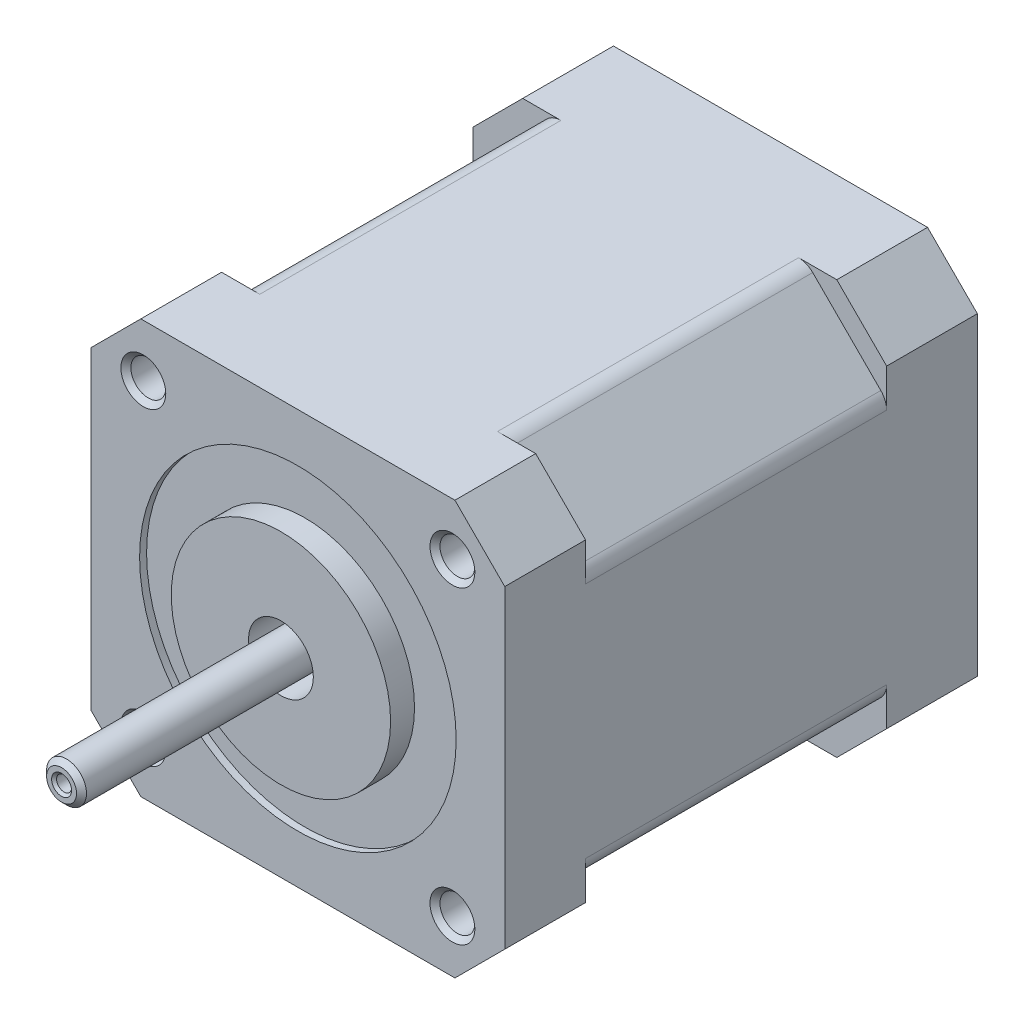
SolidWorks part; units mm, degrees
ref_plane "Front Plane" through (0, 0, 0) normal (0, 0, 1) x (1, 0, 0)
ref_plane "Top Plane" through (0, 0, 0) normal (0, 1, 0) x (1, 0, 0)
ref_plane "Right Plane" through (0, 0, 0) normal (1, 0, 0) x (0, 0, -1)
sketch "Sketch1" plane through (0, 0, 0) normal (0, 0, 1) x (1, 0, 0)
  line L0 (15.75, 20.75) -> (20.75, 15.75)
  line L1 (-15.75, 20.75) -> (15.75, 20.75)
  line L2 (-20.75, 15.75) -> (-20.75, -15.75)
  line L3 (-15.75, -20.75) -> (15.75, -20.75)
  line L4 (20.75, 15.75) -> (20.75, -15.75)
  line L5 (-20.75, 20.75) -> (20.75, -20.75) construction
  line L6 (-20.75, -20.75) -> (20.75, 20.75) construction
  line L7 (-20.75, 15.75) -> (-15.75, 20.75)
  line L8 (-20.75, -15.75) -> (-15.75, -20.75)
  line L9 (15.75, -20.75) -> (20.75, -15.75)
  point P0 (0, 0)
  dimension "D1" = 41.5
  dimension "D2" = 41.5
extrude "Boss-Extrude1" add sketch "Sketch1" along normal blind 9.1
sketch "Sketch2" plane through (0, 0, 9.1) normal (0, 0, 1) x (1, 0, 0)
  line L0 (13.3358, 20.1642) -> (20.1642, 13.3358)
  line L1 (-11.9216, -20.75) -> (11.9216, -20.75)
  line L2 (-20.75, -11.9216) -> (-20.75, 11.9216)
  line L3 (-11.9216, 20.75) -> (11.9216, 20.75)
  line L4 (20.75, -11.9216) -> (20.75, 11.9216)
  line L5 (-20.75, -20.75) -> (20.75, 20.75) construction
  line L6 (-20.75, 20.75) -> (20.75, -20.75) construction
  line L7 (-20.1642, 13.3358) -> (-13.3358, 20.1642)
  line L8 (-20.1642, -13.3358) -> (-13.3358, -20.1642)
  line L9 (13.3358, -20.1642) -> (20.1642, -13.3358)
  arc A0 (-13.3358, -20.1642) -> (-11.9216, -20.75) centre (-11.9216, -18.75) ccw
  arc A1 (-20.1642, -13.3358) -> (-20.75, -11.9216) centre (-18.75, -11.9216) cw
  arc A2 (-20.1642, 13.3358) -> (-20.75, 11.9216) centre (-18.75, 11.9216) ccw
  arc A3 (-13.3358, 20.1642) -> (-11.9216, 20.75) centre (-11.9216, 18.75) cw
  arc A4 (13.3358, 20.1642) -> (11.9216, 20.75) centre (11.9216, 18.75) ccw
  arc A5 (20.1642, 13.3358) -> (20.75, 11.9216) centre (18.75, 11.9216) cw
  arc A6 (20.1642, -13.3358) -> (20.75, -11.9216) centre (18.75, -11.9216) ccw
  arc A7 (13.3358, -20.1642) -> (11.9216, -20.75) centre (11.9216, -18.75) cw
  point P0 (0, 0)
  point P16 (-12.75, -20.75)
  point P19 (-20.75, -12.75)
  point P22 (-20.75, 12.75)
  point P25 (-12.75, 20.75)
  point P28 (12.75, 20.75)
  point P31 (20.75, 12.75)
  point P34 (20.75, -12.75)
  point P37 (12.75, -20.75)
  dimension "D3" = 2
  dimension "D1" = 41.5
  dimension "D2" = 41.5
extrude "Boss-Extrude2" add sketch "Sketch2" along normal blind 30.2
sketch "Sketch3" plane through (0, 0, 39.3) normal (0, 0, 1) x (1, 0, 0)
  line L0 (15.75, 20.75) -> (20.75, 15.75)
  line L1 (-15.75, -20.75) -> (15.75, -20.75)
  line L2 (-20.75, -15.75) -> (-20.75, 15.75)
  line L3 (-15.75, 20.75) -> (15.75, 20.75)
  line L4 (20.75, -15.75) -> (20.75, 15.75)
  line L5 (-20.75, -20.75) -> (20.75, 20.75) construction
  line L6 (-20.75, 20.75) -> (20.75, -20.75) construction
  line L7 (-20.75, 15.75) -> (-15.75, 20.75)
  line L8 (-20.75, -15.75) -> (-15.75, -20.75)
  line L9 (15.75, -20.75) -> (20.75, -15.75)
  point P0 (0, 0)
  dimension "D1" = 41.5
  dimension "D2" = 41.5
extrude "Boss-Extrude3" add sketch "Sketch3" along normal blind 8.1
sketch "Sketch4" plane through (0, 0, 47.4) normal (0, 0, 1) x (1, 0, 0)
  circle A0 centre (0, 0) radius 15.875
  dimension "D1" = 31.75
extrude "Cut-Extrude1" cut sketch "Sketch4" against normal blind 0.7
sketch "Sketch5" plane through (0, 0, 46.7) normal (0, 0, 1) x (1, 0, 0)
  circle A0 centre (0, 0) radius 11
  dimension "D1" = 22
extrude "Boss-Extrude4" add sketch "Sketch5" along normal blind 2.4
sketch "Sketch6" plane through (0, 0, 0) normal (0, 0, -1) x (-1, 0, 0)
  line L9 (0, 0) -> (14.2626, 14.2626) construction
  circle A0 centre (-15.5, 15.5) radius 1.75
  circle A1 centre (-15.5, -15.5) radius 1.75
  circle A2 centre (15.5, -15.5) radius 1.75
  circle A3 centre (15.5, 15.5) radius 1.75
  point P0 (0, 0)
  dimension "D3" = 3.5
  dimension "D4" = 3.5
  dimension "D5" = 3.5
  dimension "D6" = 3.5
  dimension "D1" = 31
  dimension "D2" = 31
extrude "Cut-Extrude2" cut sketch "Sketch6" against normal through all
chamfer "Chamfer1" distance 0.5 angle 45 8 edges at (13.75, -15.5, 0) (17.25, -15.5, 47.4) (-17.25, -15.5, 0) (-13.75, -15.5, 47.4) (-17.25, 15.5, 0) (-13.75, 15.5, 47.4) (13.75, 15.5, 0) (17.25, 15.5, 47.4)
sketch "Sketch7" plane through (0, 0, 0) normal (0, 0, -1) x (-1, 0, 0)
  circle A0 centre (0, 0) radius 3.95
  dimension "D1" = 7.9
extrude "Cut-Extrude3" cut sketch "Sketch7" against normal blind 3.3
sketch "Sketch8" plane through (0, 0, 49.1) normal (0, 0, 1) x (1, 0, 0)
  circle A0 centre (0, 0) radius 3.25
  dimension "D1" = 6.5
extrude "Cut-Extrude4" cut sketch "Sketch8" against normal blind 5
sketch "Sketch9" plane through (0, 0, 44.1) normal (0, 0, 1) x (1, 0, 0)
  circle A0 centre (0, 0) radius 2
  dimension "D1" = 4
extrude "Boss-Extrude5" add sketch "Sketch9" along normal blind 27
chamfer "Chamfer2" distance 0.5 angle 45 1 edges at (2, 0, 71.1)
sketch "Sketch10" plane through (0, 0, 71.1) normal (0, 0, 1) x (1, 0, 0)
  circle A0 centre (0, 0) radius 0.75
  dimension "D1" = 1.5
extrude "Cut-Extrude5" cut sketch "Sketch10" against normal blind 3
chamfer "Chamfer3" distance 0.25 angle 45 1 edges at (0.75, 0, 71.1)
sketch "Sketch11" plane through (0, 0, 3.3) normal (0, 0, -1) x (-1, 0, 0)
  circle A0 centre (0, 0) radius 2.5
  dimension "D1" = 5
extrude "Boss-Extrude6" add sketch "Sketch11" along normal blind 0.5
chamfer "Chamfer4" distance 0.5 angle 45 1 edges at (-2.5, 0, 2.8)
sketch "Sketch12" plane through (0, 0, 2.8) normal (0, 0, -1) x (-1, 0, 0)
  circle A0 centre (0, 0) radius 0.75
  dimension "D1" = 1.5
extrude "Cut-Extrude6" cut sketch "Sketch12" against normal blind 3
chamfer "Chamfer5" distance 0.25 angle 45 1 edges at (-0.75, 0, 2.8)
sketch "Sketch14" plane through (0, -20.75, 0) normal (0, -1, 0) x (1, 0, 0)
  line L0 (-15.75, 0) -> (15.75, 0) construction
  line L1 (-4, 1) -> (4, 1)
  line L2 (-4, 1) -> (-4, 8.1)
  line L3 (-4, 8.1) -> (4, 8.1)
  line L4 (4, 1) -> (4, 8.1)
  dimension "D1" = 8
  dimension "D2" = 7.1
  dimension "D3" = 1
  dimension "D4" = 4
extrude "Cut-Extrude8" cut sketch "Sketch14" against normal blind 5
